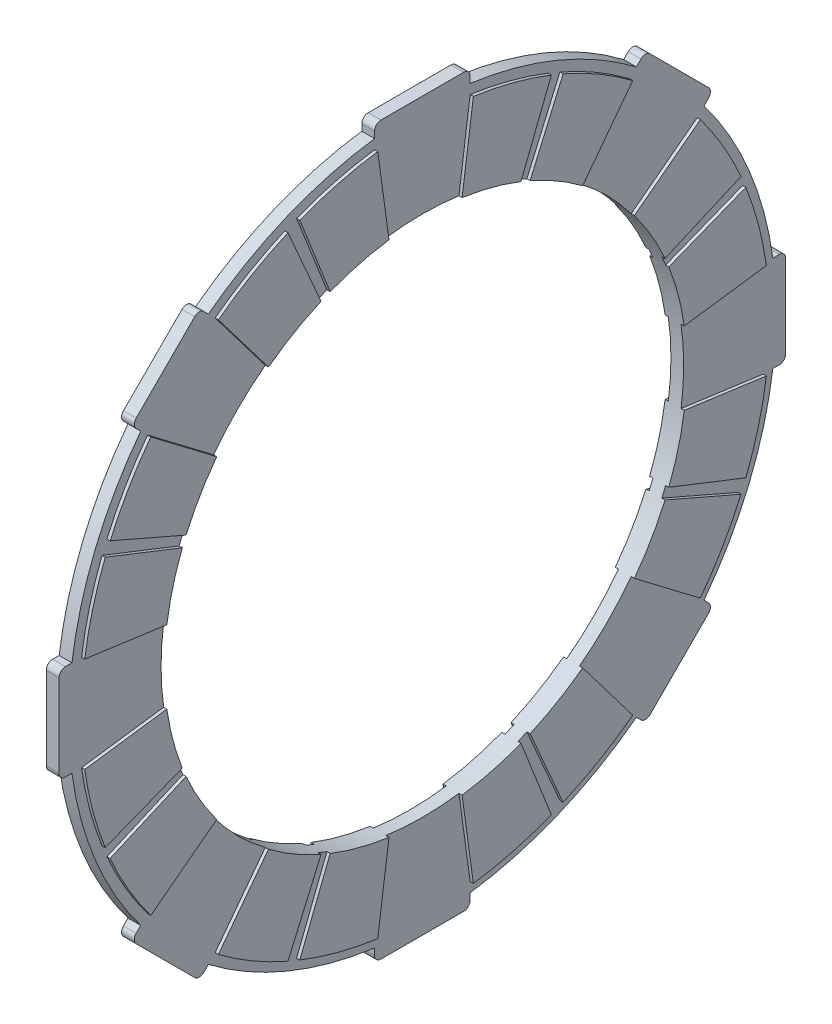
SolidWorks part; units mm, degrees
material "AISI 1075 spring steel"
ref_plane "Front Plane" through (0, 0, 0) normal (1, 0, 0) x (0, 1, 0)
ref_plane "Top Plane" through (0, 0, 0) normal (0, 0, 1) x (0, 1, 0)
ref_plane "Right Plane" through (0, 0, 0) normal (0, 1, 0) x (-1, 0, 0)
sketch "Sketch2" plane through (0, 0, 0) normal (1, 0, 0) x (0, 1, 0)
  line L0 (0, 65.4477) -> (0, -66.0234) construction
  line L1 (-63.201, 0) -> (63.4719, 0) construction
  line L2 (-7.5, 57.01) -> (7.5, 57.01)
  line L3 (-7.5, 57.01) -> (-7.5, 53.4766)
  line L5 (7.5, 53.4766) -> (7.5, 57.01)
  circle A0 centre (0, 0) radius 54
  circle A1 centre (0, 0) radius 41
  circle A2 centre (0, 0) radius 55.5
  point P10 (0, 57.01)
  dimension "D1" = 108
  dimension "D2" = 82
  dimension "D5" = 111
  dimension "D3" = 57.01
  dimension "D4" = 15
extrude "Boss-Extrude1" add sketch "Sketch2" along normal mid plane 2 contours A0 A1 | L3 A2 L5 A0 | L5 A2 L3 A0 region at (0, 0, 54.5778) region at (0, -9.0662, 54.2338) region at (0, 0, 52.4726)
extrude "Boss-Extrude2" add sketch "Sketch2<3>" along normal mid plane 2 contours A2 L5 L2 L3 region at (0, 0, 56.1635)
sketch "Sketch2<3>" plane through (0, 0, 0) normal (1, 0, 0) x (0, 1, 0) same geometry as "Sketch2"
fillet "Fillet1" radius 1 2 edges at (0, -7.5, 57.01) (0, 7.5, 57.01)
pattern_circular "CirPattern1" count 8 over 360 about axis through (1, 0, 0) along (1, 0, 0) of "Fillet1", "Boss-Extrude2"
sketch "Sketch3" plane through (1, 0, 0) normal (1, 0, 0) x (0, 1, 0)
  line L0 (0, 62.3071) -> (0, -72.3749) construction
  line L1 (-70.6509, 0) -> (74.3342, 0) construction
  line L2 (-7.5, 53.4766) -> (-5.7357, 40.5968)
  line L3 (-19.7375, 50.2636) -> (-14.973, 38.1682)
  line L4 (4.9018, 40.7059) -> (7.5, 53.4766)
  line L5 (-21.5852, 49.4983) -> (-16.4015, 37.5765)
  line L6 (-32.5104, 43.117) -> (-24.6505, 32.762)
  line L7 (14.1866, 38.4674) -> (19.7375, 50.2636)
  line L8 (21.5852, 49.4983) -> (15.6271, 37.905)
  line L9 (32.5104, 43.117) -> (23.9729, 33.2611)
  line L13 (-33.5811, 44.1877) -> (-34.3017, 44.9084) construction
  line L14 (-7.5, 56.01) -> (-7.5, 54.9909) construction
  line L15 (0, 0) -> (-20.6649, 49.8895) construction
  line L16 (7.5, 54.9909) -> (7.5, 56.01) construction
  line L17 (34.3017, 44.9084) -> (33.5811, 44.1877) construction
  line L18 (0, 0) -> (27.4544, 66.2808) construction
  circle A0 centre (0, 0) radius 54 construction
  circle A1 centre (0, 0) radius 54
  circle A2 centre (0, 0) radius 41 construction
  circle A3 centre (0, 0) radius 41
  circle A4 centre (0, 0) radius 40 construction
  circle M62 centre (0, 0) radius 41
  dimension "D1" = 80
  dimension "D2" = 7.8
  dimension "D3" = 11.5
  dimension "D4" = 13.7
  dimension "D5" = 2
  dimension "D6" = 13.7
  dimension "D7" = 13.7
  dimension "D8" = 13.7
  dimension "D9" = 2
  dimension "D10" = 14.7
  dimension "D11" = 1
  dimension "D12" = 1
  dimension "D13" = 22.5
  dimension "D14" = 1
  dimension "D15" = 1
extrude "Boss-Extrude3" add sketch "Sketch3" along normal blind 0.5 and the other way blind 2.5 contours L5 A1 L6 M62 | L2 A1 L3 M62 region at (1, -12.118, 46.1282) region at (1, -24.0488, 41.1863)
pattern_circular "CirPattern2" count 8 over 360 about axis through (1, 0, 0) along (1, 0, 0) of "Boss-Extrude3"
ref_axis "Axis1" through (-1.65, 0, 0) along (1, 0, 0)
